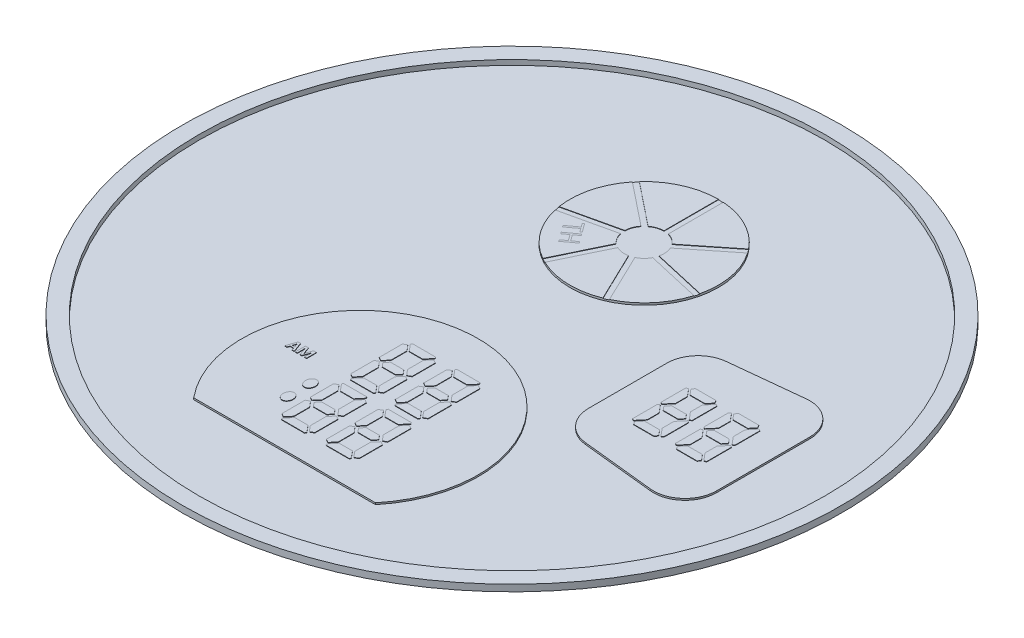
SolidWorks part; units mm, degrees
note: The reader was unsure of these and kept them because the rebuilt part matched: shared geometry of "Sketch2<5>".
ref_plane "Front Plane" through (0, 0, 0) normal (0, 0, 1) x (1, 0, 0)
ref_plane "Top Plane" through (0, 0, 0) normal (0, 1, 0) x (1, 0, 0)
ref_plane "Right Plane" through (0, 0, 0) normal (1, 0, 0) x (0, 0, -1)
sketch "Sketch1" plane through (0, 0, 0) normal (0, 1, 0) x (1, 0, 0)
  line L0 (13.2477, 3.3274) -> (8.8477, 2.8649) construction
  line L1 (13.8, -2.8301) -> (13.8, 2.8301) construction
  line L2 (8.8477, -2.8649) -> (13.2477, -3.3274) construction
  line L3 (8.4, 2.3677) -> (8.4, -2.3677) construction
  line L4 (13.2477, 3.3274) -> (8.8477, 2.8649)
  line L5 (13.8, -2.8301) -> (13.8, 2.8301)
  line L6 (8.8477, -2.8649) -> (13.2477, -3.3274)
  line L7 (8.4, 2.3677) -> (8.4, -2.3677)
  line L8 (-4.8, -12.3658) -> (4.8, -12.3658)
  circle A0 centre (0, 0) radius 19.95 construction
  circle A1 centre (0, 0) radius 19.95
  circle A2 centre (0, 8) radius 3.9422 construction
  circle A3 centre (0, 8) radius 3.9422
  arc A4 (4.8, -12.3658) -> (-4.8, -12.3658) centre (0, -9.2) ccw construction
  arc A5 (4.8, -12.3658) -> (-4.8, -12.3658) centre (0, -9.2) ccw
  arc A6 (13.8, 2.8301) -> (13.2477, 3.3274) centre (13.3, 2.8301) ccw construction
  arc A7 (8.8477, 2.8649) -> (8.4, 2.3677) centre (8.9, 2.3677) ccw construction
  arc A8 (13.2477, -3.3274) -> (13.8, -2.8301) centre (13.3, -2.8301) ccw construction
  arc A9 (8.4, -2.3677) -> (8.8477, -2.8649) centre (8.9, -2.3677) ccw construction
  arc A10 (13.8, 2.8301) -> (13.2477, 3.3274) centre (13.3, 2.8301) ccw
  arc A11 (8.8477, 2.8649) -> (8.4, 2.3677) centre (8.9, 2.3677) ccw
  arc A12 (13.2477, -3.3274) -> (13.8, -2.8301) centre (13.3, -2.8301) ccw
  arc A13 (8.4, -2.3677) -> (8.8477, -2.8649) centre (8.9, -2.3677) ccw
extrude "Boss-Extrude1" add sketch "Sketch1" along normal blind 0.1 contours A1 A13 L7 A11 L4 A10 L5 A12 L6 A5 L8 A3 | A3 | L8 A5 | L7 A13 L6 A12 L5 A10 L4 A11
sketch "Sketch2" plane through (0, 0.1, 0) normal (0, 1, 0) x (1, 0, 0)
  line L0 (-4.8, -12.3658) -> (4.8, -12.3658) construction
  line L1 (-4.8, -12.3658) -> (4.8, -12.3658) construction
  line L2 (13.2477, 3.3274) -> (8.8477, 2.8649) construction
  line L3 (13.8, -2.8301) -> (13.8, 2.8301) construction
  line L4 (8.8477, -2.8649) -> (13.2477, -3.3274) construction
  line L5 (8.4, 2.3677) -> (8.4, -2.3677) construction
  line L6 (13.2477, 3.3274) -> (8.8477, 2.8649) construction
  line L7 (13.8, -2.8301) -> (13.8, 2.8301) construction
  line L8 (8.8477, -2.8649) -> (13.2477, -3.3274) construction
  line L9 (8.4, 2.3677) -> (8.4, -2.3677) construction
  line L10 (0, 8) -> (0, 12.5) construction
  line L11 (0, 8) -> (-3.5182, 10.8057) construction
  line L12 (0, 8) -> (0, 12.5) construction
  line L13 (0, 8) -> (3.5182, 10.8057) construction
  line L14 (0, 8) -> (4.3872, 6.9987) construction
  line L15 (0, 8) -> (1.9525, 3.9456) construction
  line L16 (0, 8) -> (-1.9525, 3.9456) construction
  line L17 (0, 8) -> (-4.3872, 6.9987) construction
  line L18 (8, 2.3677) -> (8, -2.3677) construction
  line L19 (8.8059, -3.2627) -> (13.2059, -3.7252) construction
  line L20 (14.2, -2.8301) -> (14.2, 2.8301) construction
  line L21 (13.2059, 3.7252) -> (8.8059, 3.2627) construction
  line L22 (-5.0107, -12.7658) -> (5.0107, -12.7658) construction
  line L23 (-2.7, -4.1233) -> (-2.7, -12.3658) construction
  line L24 (-2.7, -8.3) -> (5.6791, -8.3) construction
  line L25 (-0.2, -6.2567) -> (-0.4893, -6.6014)
  line L26 (-0.4893, -6.6014) -> (-0.4893, -7.5553)
  line L27 (-0.4893, -7.5553) -> (-0.2, -7.9)
  line L28 (-0.2, -7.9) -> (0.0107, -7.7783)
  line L29 (0.0107, -7.7783) -> (0.0107, -6.3783)
  line L30 (0.0107, -6.3783) -> (-0.2, -6.2567)
  line L31 (-0.9329, -6.2167) -> (-0.442, -6.2167) construction
  line L32 (0.0107, -6.055) -> (-0.2, -6.1767)
  line L33 (-0.2, -6.1767) -> (-0.4893, -5.8319)
  line L34 (0.0107, -4.655) -> (0.0107, -6.055)
  line L35 (-0.2, -4.5333) -> (0.0107, -4.655)
  line L36 (-0.4893, -4.878) -> (-0.2, -4.5333)
  line L37 (-0.4893, -5.8319) -> (-0.4893, -4.878)
  line L38 (-0.5823, -7.6) -> (-0.2354, -8.0134)
  line L39 (-0.2354, -8.0134) -> (-0.2854, -8.1)
  line L40 (-0.2854, -8.1) -> (-1.6854, -8.1)
  line L41 (-1.6854, -8.1) -> (-1.7354, -8.0134)
  line L42 (-1.7354, -8.0134) -> (-1.3885, -7.6)
  line L43 (-1.3885, -7.6) -> (-0.5823, -7.6)
  line L44 (-0.3725, -6.2167) -> (-0.5823, -5.9667)
  line L45 (-0.5823, -5.9667) -> (-1.3885, -5.9667)
  line L46 (-1.3885, -5.9667) -> (-1.5983, -6.2167)
  line L47 (-1.5983, -6.2167) -> (-1.3885, -6.4667)
  line L48 (-1.3885, -6.4667) -> (-0.5823, -6.4667)
  line L49 (-0.5823, -6.4667) -> (-0.3725, -6.2167)
  line L50 (-1.3885, -5.9667) -> (-1.3885, -6.4667) construction
  line L51 (-0.9854, -7.6) -> (-0.9854, -7.1638) construction
  line L52 (-0.4893, -6.6014) -> (-0.4893, -7.5553)
  line L53 (-0.4893, -7.5553) -> (-0.2, -7.9)
  line L54 (-0.2, -7.9) -> (0.0107, -7.7783)
  line L55 (0.0107, -7.7783) -> (0.0107, -6.3783)
  line L56 (-0.2, -6.2567) -> (-0.4893, -6.6014)
  line L57 (0.0107, -6.3783) -> (-0.2, -6.2567)
  line L58 (0.0107, -6.055) -> (-0.2, -6.1767)
  line L59 (0.0107, -4.655) -> (0.0107, -6.055)
  line L60 (-0.2, -4.5333) -> (0.0107, -4.655)
  line L61 (-0.4893, -4.878) -> (-0.2, -4.5333)
  line L62 (-0.4893, -5.8319) -> (-0.4893, -4.878)
  line L63 (-0.2, -6.1767) -> (-0.4893, -5.8319)
  line L64 (-1.7708, -6.1767) -> (-1.4815, -5.8319)
  line L65 (-1.4815, -5.8319) -> (-1.4815, -4.878)
  line L66 (-1.4815, -4.878) -> (-1.7708, -4.5333)
  line L67 (-1.7708, -4.5333) -> (-1.9815, -4.655)
  line L68 (-1.9815, -4.655) -> (-1.9815, -6.055)
  line L69 (-1.9815, -6.055) -> (-1.7708, -6.1767)
  line L70 (-1.9815, -6.3783) -> (-1.7708, -6.2567)
  line L71 (-1.7708, -6.2567) -> (-1.4815, -6.6014)
  line L72 (-1.9815, -7.7783) -> (-1.9815, -6.3783)
  line L73 (-1.7708, -7.9) -> (-1.9815, -7.7783)
  line L74 (-1.4815, -7.5553) -> (-1.7708, -7.9)
  line L75 (-1.4815, -6.6014) -> (-1.4815, -7.5553)
  line L76 (-1.4815, -5.8319) -> (-1.4815, -4.878)
  line L77 (-1.4815, -4.878) -> (-1.7708, -4.5333)
  line L78 (-1.7708, -4.5333) -> (-1.9815, -4.655)
  line L79 (-1.9815, -4.655) -> (-1.9815, -6.055)
  line L80 (-1.7708, -6.1767) -> (-1.4815, -5.8319)
  line L81 (-1.9815, -6.055) -> (-1.7708, -6.1767)
  line L82 (-1.9815, -6.3783) -> (-1.7708, -6.2567)
  line L83 (-1.9815, -7.7783) -> (-1.9815, -6.3783)
  line L84 (-1.7708, -7.9) -> (-1.9815, -7.7783)
  line L85 (-1.4815, -7.5553) -> (-1.7708, -7.9)
  line L86 (-1.4815, -6.6014) -> (-1.4815, -7.5553)
  line L87 (-1.7708, -6.2567) -> (-1.4815, -6.6014)
  line L88 (-0.2354, -4.4199) -> (-0.2854, -4.3333)
  line L89 (-0.5823, -4.8333) -> (-0.2354, -4.4199)
  line L90 (-1.3885, -4.8333) -> (-0.5823, -4.8333)
  line L91 (-0.2854, -4.3333) -> (-1.6854, -4.3333)
  line L92 (-1.6854, -4.3333) -> (-1.7354, -4.4199)
  line L93 (-1.7354, -4.4199) -> (-1.3885, -4.8333)
  line L94 (0.3607, -9.2447) -> (0.3607, -7.3553) construction
  line L95 (1.7069, -7.6) -> (1.7069, -7.1638) construction
  line L96 (2.11, -5.9667) -> (2.11, -6.4667) construction
  line L97 (1.6544, -6.2167) -> (1.1635, -6.2167) construction
  line L98 (2.4569, -4.4199) -> (2.11, -4.8333)
  line L99 (2.4069, -4.3333) -> (2.4569, -4.4199)
  line L100 (1.0069, -4.3333) -> (2.4069, -4.3333)
  line L101 (2.11, -4.8333) -> (1.3038, -4.8333)
  line L102 (1.3038, -4.8333) -> (0.9569, -4.4199)
  line L103 (0.9569, -4.4199) -> (1.0069, -4.3333)
  line L104 (2.4923, -6.2567) -> (2.203, -6.6014)
  line L105 (2.203, -6.6014) -> (2.203, -7.5553)
  line L106 (2.203, -7.5553) -> (2.4923, -7.9)
  line L107 (2.4923, -7.9) -> (2.703, -7.7783)
  line L108 (2.703, -7.7783) -> (2.703, -6.3783)
  line L109 (2.703, -6.3783) -> (2.4923, -6.2567)
  line L110 (2.703, -6.055) -> (2.4923, -6.1767)
  line L111 (2.4923, -6.1767) -> (2.203, -5.8319)
  line L112 (2.703, -4.655) -> (2.703, -6.055)
  line L113 (2.4923, -4.5333) -> (2.703, -4.655)
  line L114 (2.203, -4.878) -> (2.4923, -4.5333)
  line L115 (2.203, -5.8319) -> (2.203, -4.878)
  line L116 (2.203, -6.6014) -> (2.203, -7.5553)
  line L117 (2.203, -7.5553) -> (2.4923, -7.9)
  line L118 (2.4923, -7.9) -> (2.703, -7.7783)
  line L119 (2.703, -7.7783) -> (2.703, -6.3783)
  line L120 (2.4923, -6.2567) -> (2.203, -6.6014)
  line L121 (2.703, -6.3783) -> (2.4923, -6.2567)
  line L122 (2.703, -6.055) -> (2.4923, -6.1767)
  line L123 (2.703, -4.655) -> (2.703, -6.055)
  line L124 (2.4923, -4.5333) -> (2.703, -4.655)
  line L125 (2.203, -4.878) -> (2.4923, -4.5333)
  line L126 (2.203, -5.8319) -> (2.203, -4.878)
  line L127 (2.4923, -6.1767) -> (2.203, -5.8319)
  line L128 (0.9215, -6.1767) -> (1.2107, -5.8319)
  line L129 (1.2107, -5.8319) -> (1.2107, -4.878)
  line L130 (1.2107, -4.878) -> (0.9215, -4.5333)
  line L131 (0.9215, -4.5333) -> (0.7107, -4.655)
  line L132 (0.7107, -4.655) -> (0.7107, -6.055)
  line L133 (0.7107, -6.055) -> (0.9215, -6.1767)
  line L134 (0.7107, -6.3783) -> (0.9215, -6.2567)
  line L135 (0.9215, -6.2567) -> (1.2107, -6.6014)
  line L136 (0.7107, -7.7783) -> (0.7107, -6.3783)
  line L137 (0.9215, -7.9) -> (0.7107, -7.7783)
  line L138 (1.2107, -7.5553) -> (0.9215, -7.9)
  line L139 (1.2107, -6.6014) -> (1.2107, -7.5553)
  line L140 (1.3038, -6.4667) -> (1.094, -6.2167)
  line L141 (2.11, -6.4667) -> (1.3038, -6.4667)
  line L142 (2.3198, -6.2167) -> (2.11, -6.4667)
  line L143 (2.11, -5.9667) -> (2.3198, -6.2167)
  line L144 (1.3038, -5.9667) -> (2.11, -5.9667)
  line L145 (1.094, -6.2167) -> (1.3038, -5.9667)
  line L146 (2.11, -7.6) -> (1.3038, -7.6)
  line L147 (2.4569, -8.0134) -> (2.11, -7.6)
  line L148 (2.4069, -8.1) -> (2.4569, -8.0134)
  line L149 (1.0069, -8.1) -> (2.4069, -8.1)
  line L150 (0.9569, -8.0134) -> (1.0069, -8.1)
  line L151 (1.3038, -7.6) -> (0.9569, -8.0134)
  line L152 (1.2107, -5.8319) -> (1.2107, -4.878)
  line L153 (1.2107, -4.878) -> (0.9215, -4.5333)
  line L154 (0.9215, -4.5333) -> (0.7107, -4.655)
  line L155 (0.7107, -4.655) -> (0.7107, -6.055)
  line L156 (0.9215, -6.1767) -> (1.2107, -5.8319)
  line L157 (0.7107, -6.055) -> (0.9215, -6.1767)
  line L158 (0.7107, -6.3783) -> (0.9215, -6.2567)
  line L159 (0.7107, -7.7783) -> (0.7107, -6.3783)
  line L160 (0.9215, -7.9) -> (0.7107, -7.7783)
  line L161 (1.2107, -7.5553) -> (0.9215, -7.9)
  line L162 (1.2107, -6.6014) -> (1.2107, -7.5553)
  line L163 (0.9215, -6.2567) -> (1.2107, -6.6014)
  line L164 (-0.4893, -7.0783) -> (0.0107, -7.0783) construction
  line L165 (-1.3885, -7.6) -> (-1.3885, -8.1) construction
  line L166 (-1.3885, -9) -> (-1.3885, -8.5) construction
  line L167 (-0.4893, -9.5217) -> (0.0107, -9.5217) construction
  line L168 (1.6544, -10.3833) -> (1.1635, -10.3833) construction
  line L169 (2.11, -10.6333) -> (2.11, -10.1333) construction
  line L170 (1.7069, -9) -> (1.7069, -9.4362) construction
  line L171 (-0.9854, -9) -> (-0.9854, -9.4362) construction
  line L172 (-1.3885, -10.6333) -> (-1.3885, -10.1333) construction
  line L173 (-0.9329, -10.3833) -> (-0.442, -10.3833) construction
  line L174 (0.9215, -10.3433) -> (1.2107, -9.9986)
  line L175 (1.2107, -9.9986) -> (1.2107, -9.0447)
  line L176 (1.2107, -9.0447) -> (0.9215, -8.7)
  line L177 (0.9215, -8.7) -> (0.7107, -8.8217)
  line L178 (0.7107, -8.8217) -> (0.7107, -10.2217)
  line L179 (0.7107, -10.2217) -> (0.9215, -10.3433)
  line L180 (0.7107, -10.545) -> (0.9215, -10.4233)
  line L181 (0.9215, -10.4233) -> (1.2107, -10.7681)
  line L182 (0.7107, -11.945) -> (0.7107, -10.545)
  line L183 (0.9215, -12.0667) -> (0.7107, -11.945)
  line L184 (1.2107, -11.722) -> (0.9215, -12.0667)
  line L185 (1.2107, -10.7681) -> (1.2107, -11.722)
  line L186 (1.3038, -9) -> (0.9569, -8.5866)
  line L187 (0.9569, -8.5866) -> (1.0069, -8.5)
  line L188 (1.0069, -8.5) -> (2.4069, -8.5)
  line L189 (2.4069, -8.5) -> (2.4569, -8.5866)
  line L190 (2.4569, -8.5866) -> (2.11, -9)
  line L191 (2.11, -9) -> (1.3038, -9)
  line L192 (1.094, -10.3833) -> (1.3038, -10.6333)
  line L193 (1.3038, -10.6333) -> (2.11, -10.6333)
  line L194 (2.11, -10.6333) -> (2.3198, -10.3833)
  line L195 (2.3198, -10.3833) -> (2.11, -10.1333)
  line L196 (2.11, -10.1333) -> (1.3038, -10.1333)
  line L197 (1.3038, -10.1333) -> (1.094, -10.3833)
  line L198 (1.2107, -9.9986) -> (1.2107, -9.0447)
  line L199 (1.2107, -9.0447) -> (0.9215, -8.7)
  line L200 (0.9215, -8.7) -> (0.7107, -8.8217)
  line L201 (0.7107, -8.8217) -> (0.7107, -10.2217)
  line L202 (0.9215, -10.3433) -> (1.2107, -9.9986)
  line L203 (0.7107, -10.2217) -> (0.9215, -10.3433)
  line L204 (0.7107, -10.545) -> (0.9215, -10.4233)
  line L205 (0.7107, -11.945) -> (0.7107, -10.545)
  line L206 (0.9215, -12.0667) -> (0.7107, -11.945)
  line L207 (1.2107, -11.722) -> (0.9215, -12.0667)
  line L208 (1.2107, -10.7681) -> (1.2107, -11.722)
  line L209 (0.9215, -10.4233) -> (1.2107, -10.7681)
  line L210 (2.4923, -10.4233) -> (2.203, -10.7681)
  line L211 (2.203, -10.7681) -> (2.203, -11.722)
  line L212 (2.203, -11.722) -> (2.4923, -12.0667)
  line L213 (2.4923, -12.0667) -> (2.703, -11.945)
  line L214 (2.703, -11.945) -> (2.703, -10.545)
  line L215 (2.703, -10.545) -> (2.4923, -10.4233)
  line L216 (2.703, -10.2217) -> (2.4923, -10.3433)
  line L217 (2.4923, -10.3433) -> (2.203, -9.9986)
  line L218 (2.703, -8.8217) -> (2.703, -10.2217)
  line L219 (2.4923, -8.7) -> (2.703, -8.8217)
  line L220 (2.203, -9.0447) -> (2.4923, -8.7)
  line L221 (2.203, -9.9986) -> (2.203, -9.0447)
  line L222 (2.203, -10.7681) -> (2.203, -11.722)
  line L223 (2.203, -11.722) -> (2.4923, -12.0667)
  line L224 (2.4923, -12.0667) -> (2.703, -11.945)
  line L225 (2.703, -11.945) -> (2.703, -10.545)
  line L226 (2.4923, -10.4233) -> (2.203, -10.7681)
  line L227 (2.703, -10.545) -> (2.4923, -10.4233)
  line L228 (2.703, -10.2217) -> (2.4923, -10.3433)
  line L229 (2.703, -8.8217) -> (2.703, -10.2217)
  line L230 (2.4923, -8.7) -> (2.703, -8.8217)
  line L231 (2.203, -9.0447) -> (2.4923, -8.7)
  line L232 (2.203, -9.9986) -> (2.203, -9.0447)
  line L233 (2.4923, -10.3433) -> (2.203, -9.9986)
  line L234 (0.9569, -12.1801) -> (1.0069, -12.2667)
  line L235 (1.3038, -11.7667) -> (0.9569, -12.1801)
  line L236 (2.11, -11.7667) -> (1.3038, -11.7667)
  line L237 (1.0069, -12.2667) -> (2.4069, -12.2667)
  line L238 (2.4069, -12.2667) -> (2.4569, -12.1801)
  line L239 (2.4569, -12.1801) -> (2.11, -11.7667)
  line L240 (-1.7354, -12.1801) -> (-1.3885, -11.7667)
  line L241 (-1.6854, -12.2667) -> (-1.7354, -12.1801)
  line L242 (-0.2854, -12.2667) -> (-1.6854, -12.2667)
  line L243 (-1.3885, -11.7667) -> (-0.5823, -11.7667)
  line L244 (-0.5823, -11.7667) -> (-0.2354, -12.1801)
  line L245 (-0.2354, -12.1801) -> (-0.2854, -12.2667)
  line L246 (-1.7708, -10.3433) -> (-1.4815, -9.9986)
  line L247 (-1.4815, -9.9986) -> (-1.4815, -9.0447)
  line L248 (-1.4815, -9.0447) -> (-1.7708, -8.7)
  line L249 (-1.7708, -8.7) -> (-1.9815, -8.8217)
  line L250 (-1.9815, -8.8217) -> (-1.9815, -10.2217)
  line L251 (-1.9815, -10.2217) -> (-1.7708, -10.3433)
  line L252 (-1.9815, -10.545) -> (-1.7708, -10.4233)
  line L253 (-1.7708, -10.4233) -> (-1.4815, -10.7681)
  line L254 (-1.9815, -11.945) -> (-1.9815, -10.545)
  line L255 (-1.7708, -12.0667) -> (-1.9815, -11.945)
  line L256 (-1.4815, -11.722) -> (-1.7708, -12.0667)
  line L257 (-1.4815, -10.7681) -> (-1.4815, -11.722)
  line L258 (-1.4815, -9.9986) -> (-1.4815, -9.0447)
  line L259 (-1.4815, -9.0447) -> (-1.7708, -8.7)
  line L260 (-1.7708, -8.7) -> (-1.9815, -8.8217)
  line L261 (-1.9815, -8.8217) -> (-1.9815, -10.2217)
  line L262 (-1.7708, -10.3433) -> (-1.4815, -9.9986)
  line L263 (-1.9815, -10.2217) -> (-1.7708, -10.3433)
  line L264 (-1.9815, -10.545) -> (-1.7708, -10.4233)
  line L265 (-1.9815, -11.945) -> (-1.9815, -10.545)
  line L266 (-1.7708, -12.0667) -> (-1.9815, -11.945)
  line L267 (-1.4815, -11.722) -> (-1.7708, -12.0667)
  line L268 (-1.4815, -10.7681) -> (-1.4815, -11.722)
  line L269 (-1.7708, -10.4233) -> (-1.4815, -10.7681)
  line L270 (-0.2, -10.4233) -> (-0.4893, -10.7681)
  line L271 (-0.4893, -10.7681) -> (-0.4893, -11.722)
  line L272 (-0.4893, -11.722) -> (-0.2, -12.0667)
  line L273 (-0.2, -12.0667) -> (0.0107, -11.945)
  line L274 (0.0107, -11.945) -> (0.0107, -10.545)
  line L275 (0.0107, -10.545) -> (-0.2, -10.4233)
  line L276 (0.0107, -10.2217) -> (-0.2, -10.3433)
  line L277 (-0.2, -10.3433) -> (-0.4893, -9.9986)
  line L278 (0.0107, -8.8217) -> (0.0107, -10.2217)
  line L279 (-0.2, -8.7) -> (0.0107, -8.8217)
  line L280 (-0.4893, -9.0447) -> (-0.2, -8.7)
  line L281 (-0.4893, -9.9986) -> (-0.4893, -9.0447)
  line L282 (-0.5823, -10.1333) -> (-0.3725, -10.3833)
  line L283 (-1.3885, -10.1333) -> (-0.5823, -10.1333)
  line L284 (-1.5983, -10.3833) -> (-1.3885, -10.1333)
  line L285 (-1.3885, -10.6333) -> (-1.5983, -10.3833)
  line L286 (-0.5823, -10.6333) -> (-1.3885, -10.6333)
  line L287 (-0.3725, -10.3833) -> (-0.5823, -10.6333)
  line L288 (-1.3885, -9) -> (-0.5823, -9)
  line L289 (-1.7354, -8.5866) -> (-1.3885, -9)
  line L290 (-1.6854, -8.5) -> (-1.7354, -8.5866)
  line L291 (-0.2854, -8.5) -> (-1.6854, -8.5)
  line L292 (-0.2354, -8.5866) -> (-0.2854, -8.5)
  line L293 (-0.5823, -9) -> (-0.2354, -8.5866)
  line L294 (-0.4893, -10.7681) -> (-0.4893, -11.722)
  line L295 (-0.4893, -11.722) -> (-0.2, -12.0667)
  line L296 (-0.2, -12.0667) -> (0.0107, -11.945)
  line L297 (0.0107, -11.945) -> (0.0107, -10.545)
  line L298 (-0.2, -10.4233) -> (-0.4893, -10.7681)
  line L299 (0.0107, -10.545) -> (-0.2, -10.4233)
  line L300 (0.0107, -10.2217) -> (-0.2, -10.3433)
  line L301 (0.0107, -8.8217) -> (0.0107, -10.2217)
  line L302 (-0.2, -8.7) -> (0.0107, -8.8217)
  line L303 (-0.4893, -9.0447) -> (-0.2, -8.7)
  line L304 (-0.4893, -9.9986) -> (-0.4893, -9.0447)
  line L305 (-0.2, -10.3433) -> (-0.4893, -9.9986)
  line L306 (-3.2476, -10.175) -> (-2.4, -10.175) construction
  line L307 (-5.4694, -8.3) -> (-3.8694, -8.3) construction
  line L308 (-4.8767, -8.3) -> (-5.0143, -8.3)
  line L309 (-5.0143, -8.3) -> (-5.0585, -8.161)
  line L310 (-5.0585, -8.161) -> (-5.2745, -8.161)
  line L311 (-5.2745, -8.161) -> (-5.318, -8.3)
  line L312 (-5.318, -8.3) -> (-5.4548, -8.3)
  line L313 (-5.4548, -8.3) -> (-5.2426, -7.7)
  line L314 (-5.2426, -7.7) -> (-5.0962, -7.7)
  line L315 (-5.0962, -7.7) -> (-4.8767, -8.3)
  line L316 (-5.0887, -8.0659) -> (-5.1602, -7.8554)
  line L317 (-5.1796, -7.8538) -> (-5.2467, -8.0659)
  line L318 (-5.2467, -8.0659) -> (-5.0887, -8.0659)
  line L319 (-4.2621, -8.3) -> (-4.2621, -7.9363)
  line L320 (-4.2517, -7.8098) -> (-4.2548, -7.8098)
  line L321 (-4.2735, -7.8867) -> (-4.4231, -8.3)
  line L322 (-4.4231, -8.3) -> (-4.5255, -8.3)
  line L323 (-4.5255, -8.3) -> (-4.6749, -7.8906)
  line L324 (-4.6938, -7.8098) -> (-4.6972, -7.8098)
  line L325 (-4.6938, -7.961) -> (-4.6938, -8.3)
  line L326 (-4.6938, -8.3) -> (-4.8109, -8.3)
  line L327 (-4.8109, -8.3) -> (-4.8109, -7.7)
  line L328 (-4.8109, -7.7) -> (-4.6206, -7.7)
  line L329 (-4.6206, -7.7) -> (-4.4925, -8.0627)
  line L330 (-4.4705, -8.1471) -> (-4.4679, -8.1471)
  line L331 (-4.4431, -8.0619) -> (-4.3133, -7.7)
  line L332 (-4.3133, -7.7) -> (-4.1377, -7.7)
  line L333 (-4.1377, -7.7) -> (-4.1377, -8.3)
  line L334 (-4.1377, -8.3) -> (-4.2621, -8.3)
  line L335 (10.6804, -0.0329) -> (10.2948, -0.4925)
  line L336 (10.2948, -0.4925) -> (10.2948, -1.2053)
  line L337 (10.2948, -1.2053) -> (10.6804, -1.6649)
  line L338 (10.6804, -1.6649) -> (10.7948, -1.5989)
  line L339 (10.7948, -1.5989) -> (10.7948, -0.0989)
  line L340 (10.7948, -0.0989) -> (10.6804, -0.0329)
  line L341 (10.4231, 0.0071) -> (10.9141, 0.0071) construction
  line L342 (10.7948, 0.1131) -> (10.6804, 0.0471)
  line L343 (10.6804, 0.0471) -> (10.2948, 0.5067)
  line L344 (10.7948, 1.6131) -> (10.7948, 0.1131)
  line L345 (10.6804, 1.6791) -> (10.7948, 1.6131)
  line L346 (10.2948, 1.2195) -> (10.6804, 1.6791)
  line L347 (10.2948, 0.5067) -> (10.2948, 1.2195)
  line L348 (10.2982, -1.3649) -> (10.5724, -1.6917)
  line L349 (10.5724, -1.6917) -> (10.4724, -1.8649)
  line L350 (10.4724, -1.8649) -> (9.2224, -1.8649)
  line L351 (9.2224, -1.8649) -> (9.1224, -1.6917)
  line L352 (9.1224, -1.6917) -> (9.3966, -1.3649)
  line L353 (9.3966, -1.3649) -> (10.2982, -1.3649)
  line L354 (10.5079, 0.0071) -> (10.2982, 0.2571)
  line L355 (10.2982, 0.2571) -> (9.3966, 0.2571)
  line L356 (9.3966, 0.2571) -> (9.1868, 0.0071)
  line L357 (9.1868, 0.0071) -> (9.3966, -0.2429)
  line L358 (9.3966, -0.2429) -> (10.2982, -0.2429)
  line L359 (10.2982, -0.2429) -> (10.5079, 0.0071)
  line L360 (9.3966, 0.2571) -> (9.3966, -0.2429) construction
  line L361 (9.8474, -1.3649) -> (9.8474, -1.1561) construction
  line L362 (10.2948, -0.4925) -> (10.2948, -1.2053)
  line L363 (10.2948, -1.2053) -> (10.6804, -1.6649)
  line L364 (10.6804, -1.6649) -> (10.7948, -1.5989)
  line L365 (10.7948, -1.5989) -> (10.7948, -0.0989)
  line L366 (10.6804, -0.0329) -> (10.2948, -0.4925)
  line L367 (10.7948, -0.0989) -> (10.6804, -0.0329)
  line L368 (10.7948, 0.1131) -> (10.6804, 0.0471)
  line L369 (10.7948, 1.6131) -> (10.7948, 0.1131)
  line L370 (10.6804, 1.6791) -> (10.7948, 1.6131)
  line L371 (10.2948, 1.2195) -> (10.6804, 1.6791)
  line L372 (10.2948, 0.5067) -> (10.2948, 1.2195)
  line L373 (10.6804, 0.0471) -> (10.2948, 0.5067)
  line L374 (9.0143, 0.0471) -> (9.4, 0.5067)
  line L375 (9.4, 0.5067) -> (9.4, 1.2195)
  line L376 (9.4, 1.2195) -> (9.0143, 1.6791)
  line L377 (9.0143, 1.6791) -> (8.9, 1.6131)
  line L378 (8.9, 1.6131) -> (8.9, 0.1131)
  line L379 (8.9, 0.1131) -> (9.0143, 0.0471)
  line L380 (8.9, -0.0989) -> (9.0143, -0.0329)
  line L381 (9.0143, -0.0329) -> (9.4, -0.4925)
  line L382 (8.9, -1.5989) -> (8.9, -0.0989)
  line L383 (9.0143, -1.6649) -> (8.9, -1.5989)
  line L384 (9.4, -1.2053) -> (9.0143, -1.6649)
  line L385 (9.4, -0.4925) -> (9.4, -1.2053)
  line L386 (9.4, 0.5067) -> (9.4, 1.2195)
  line L387 (9.4, 1.2195) -> (9.0143, 1.6791)
  line L388 (9.0143, 1.6791) -> (8.9, 1.6131)
  line L389 (8.9, 1.6131) -> (8.9, 0.1131)
  line L390 (9.0143, 0.0471) -> (9.4, 0.5067)
  line L391 (8.9, 0.1131) -> (9.0143, 0.0471)
  line L392 (8.9, -0.0989) -> (9.0143, -0.0329)
  line L393 (8.9, -1.5989) -> (8.9, -0.0989)
  line L394 (9.0143, -1.6649) -> (8.9, -1.5989)
  line L395 (9.4, -1.2053) -> (9.0143, -1.6649)
  line L396 (9.4, -0.4925) -> (9.4, -1.2053)
  line L397 (9.0143, -0.0329) -> (9.4, -0.4925)
  line L398 (10.5724, 1.7059) -> (10.4724, 1.8791)
  line L399 (10.2982, 1.3791) -> (10.5724, 1.7059)
  line L400 (9.3966, 1.3791) -> (10.2982, 1.3791)
  line L401 (10.4724, 1.8791) -> (9.2224, 1.8791)
  line L402 (9.2224, 1.8791) -> (9.1224, 1.7059)
  line L403 (9.1224, 1.7059) -> (9.3966, 1.3791)
  line L404 (11.1448, 0.7171) -> (11.1448, -2.2635) construction
  line L405 (12.8929, -1.3649) -> (12.8929, -1.8649) construction
  line L406 (11.9948, -0.8489) -> (11.4948, -0.8489) construction
  line L413 (12.4422, -1.3649) -> (12.4422, -1.1561) construction
  line L414 (12.8929, 0.2571) -> (12.8929, -0.2429) construction
  line L415 (11.8664, 0.0071) -> (11.3754, 0.0071) construction
  line L416 (13.1672, 1.7059) -> (12.8929, 1.3791)
  line L417 (13.0672, 1.8791) -> (13.1672, 1.7059)
  line L418 (11.8172, 1.8791) -> (13.0672, 1.8791)
  line L419 (12.8929, 1.3791) -> (11.9914, 1.3791)
  line L420 (11.9914, 1.3791) -> (11.7172, 1.7059)
  line L421 (11.7172, 1.7059) -> (11.8172, 1.8791)
  line L422 (13.2752, -0.0329) -> (12.8895, -0.4925)
  line L423 (12.8895, -0.4925) -> (12.8895, -1.2053)
  line L424 (12.8895, -1.2053) -> (13.2752, -1.6649)
  line L437 (13.2752, -1.6649) -> (13.3895, -1.5989)
  line L438 (13.3895, -1.5989) -> (13.3895, -0.0989)
  line L439 (13.3895, -0.0989) -> (13.2752, -0.0329)
  line L440 (13.3895, 0.1131) -> (13.2752, 0.0471)
  line L441 (13.2752, 0.0471) -> (12.8895, 0.5067)
  line L442 (13.3895, 1.6131) -> (13.3895, 0.1131)
  line L443 (13.2752, 1.6791) -> (13.3895, 1.6131)
  line L444 (12.8895, 1.2195) -> (13.2752, 1.6791)
  line L445 (12.8895, 0.5067) -> (12.8895, 1.2195)
  line L446 (12.8895, -0.4925) -> (12.8895, -1.2053)
  line L447 (12.8895, -1.2053) -> (13.2752, -1.6649)
  line L448 (13.2752, -1.6649) -> (13.3895, -1.5989)
  line L473 (10.2948, -0.8489) -> (10.7948, -0.8489) construction
  line L474 (9.3966, -1.3649) -> (9.3966, -1.8649) construction
  line L475 (13.3895, -1.5989) -> (13.3895, -0.0989)
  line L476 (13.2752, -0.0329) -> (12.8895, -0.4925)
  line L477 (13.3895, -0.0989) -> (13.2752, -0.0329)
  line L478 (13.3895, 0.1131) -> (13.2752, 0.0471)
  line L479 (13.3895, 1.6131) -> (13.3895, 0.1131)
  line L480 (13.2752, 1.6791) -> (13.3895, 1.6131)
  line L481 (12.8895, 1.2195) -> (13.2752, 1.6791)
  line L482 (12.8895, 0.5067) -> (12.8895, 1.2195)
  line L483 (13.2752, 0.0471) -> (12.8895, 0.5067)
  line L484 (11.6091, 0.0471) -> (11.9948, 0.5067)
  line L485 (11.9948, 0.5067) -> (11.9948, 1.2195)
  line L486 (11.9948, 1.2195) -> (11.6091, 1.6791)
  line L487 (11.6091, 1.6791) -> (11.4948, 1.6131)
  line L488 (11.4948, 1.6131) -> (11.4948, 0.1131)
  line L489 (11.4948, 0.1131) -> (11.6091, 0.0471)
  line L490 (11.4948, -0.0989) -> (11.6091, -0.0329)
  line L491 (11.6091, -0.0329) -> (11.9948, -0.4925)
  line L492 (11.4948, -1.5989) -> (11.4948, -0.0989)
  line L493 (11.6091, -1.6649) -> (11.4948, -1.5989)
  line L494 (11.9948, -1.2053) -> (11.6091, -1.6649)
  line L495 (11.9948, -0.4925) -> (11.9948, -1.2053)
  line L496 (11.9914, -0.2429) -> (11.7816, 0.0071)
  line L497 (12.8929, -0.2429) -> (11.9914, -0.2429)
  line L498 (13.1027, 0.0071) -> (12.8929, -0.2429)
  line L499 (12.8929, 0.2571) -> (13.1027, 0.0071)
  line L500 (11.9914, 0.2571) -> (12.8929, 0.2571)
  line L501 (11.7816, 0.0071) -> (11.9914, 0.2571)
  line L502 (12.8929, -1.3649) -> (11.9914, -1.3649)
  line L503 (13.1672, -1.6917) -> (12.8929, -1.3649)
  line L504 (13.0672, -1.8649) -> (13.1672, -1.6917)
  line L505 (11.8172, -1.8649) -> (13.0672, -1.8649)
  line L506 (11.7172, -1.6917) -> (11.8172, -1.8649)
  line L507 (11.9914, -1.3649) -> (11.7172, -1.6917)
  line L508 (11.9948, 0.5067) -> (11.9948, 1.2195)
  line L509 (11.9948, 1.2195) -> (11.6091, 1.6791)
  line L510 (11.6091, 1.6791) -> (11.4948, 1.6131)
  line L511 (11.4948, 1.6131) -> (11.4948, 0.1131)
  line L512 (11.6091, 0.0471) -> (11.9948, 0.5067)
  line L513 (11.4948, 0.1131) -> (11.6091, 0.0471)
  line L514 (11.4948, -0.0989) -> (11.6091, -0.0329)
  line L515 (11.4948, -1.5989) -> (11.4948, -0.0989)
  line L516 (11.6091, -1.6649) -> (11.4948, -1.5989)
  line L517 (11.9948, -1.2053) -> (11.6091, -1.6649)
  line L518 (11.9948, -0.4925) -> (11.9948, -1.2053)
  line L519 (11.6091, -0.0329) -> (11.9948, -0.4925)
  line L520 (0.3, 9.1619) -> (0.3, 12.49)
  line L521 (1.0955, 8.4899) -> (3.6975, 10.5649)
  line L522 (1.066, 7.449) -> (4.3107, 6.7084)
  line L523 (0.2338, 6.823) -> (1.6778, 3.8245)
  line L524 (-0.7744, 7.0833) -> (-2.2184, 4.0848)
  line L525 (-1.1995, 8.0339) -> (-4.4442, 7.2934)
  line L526 (-0.7214, 8.959) -> (-3.3234, 11.034)
  line L527 (0, 9.2) -> (0, 12.5)
  line L528 (0.9382, 8.7482) -> (3.5182, 10.8057)
  line L529 (1.1699, 7.733) -> (4.3872, 6.9987)
  line L530 (0.5207, 6.9188) -> (1.9525, 3.9456)
  line L531 (-0.5207, 6.9188) -> (-1.9525, 3.9456)
  line L532 (-1.1699, 7.733) -> (-4.3872, 6.9987)
  line L533 (-0.9382, 8.7482) -> (-3.5182, 10.8057)
  line L534 (8.7014, -4.2573) -> (13.1014, -4.7197)
  line L535 (15.2, -2.8301) -> (15.2, 2.8301)
  line L536 (13.1014, 4.7197) -> (8.7014, 4.2573)
  line L537 (7, 2.3677) -> (7, -2.3677)
  line L538 (-5.5023, -13.7658) -> (5.5023, -13.7658)
  circle A1 centre (0, 8) radius 4.5
  arc A2 (4.8, -12.3658) -> (-4.8, -12.3658) centre (0, -9.2) ccw construction
  arc A3 (4.8, -12.3658) -> (-4.8, -12.3658) centre (0, -9.2) ccw construction
  arc A4 (13.8, 2.8301) -> (13.2477, 3.3274) centre (13.3, 2.8301) ccw construction
  arc A5 (13.2477, -3.3274) -> (13.8, -2.8301) centre (13.3, -2.8301) ccw construction
  arc A6 (8.4, -2.3677) -> (8.8477, -2.8649) centre (8.9, -2.3677) ccw construction
  arc A7 (8.8477, 2.8649) -> (8.4, 2.3677) centre (8.9, 2.3677) ccw construction
  arc A8 (13.8, 2.8301) -> (13.2477, 3.3274) centre (13.3, 2.8301) ccw construction
  arc A9 (13.2477, -3.3274) -> (13.8, -2.8301) centre (13.3, -2.8301) ccw construction
  arc A10 (8.4, -2.3677) -> (8.8477, -2.8649) centre (8.9, -2.3677) ccw construction
  arc A11 (8.8477, 2.8649) -> (8.4, 2.3677) centre (8.9, 2.3677) ccw construction
  arc A12 (8, -2.3677) -> (8.8059, -3.2627) centre (8.9, -2.3677) ccw construction
  arc A13 (13.2059, -3.7252) -> (14.2, -2.8301) centre (13.3, -2.8301) ccw construction
  arc A14 (14.2, 2.8301) -> (13.2059, 3.7252) centre (13.3, 2.8301) ccw construction
  arc A15 (8.8059, 3.2627) -> (8, 2.3677) centre (8.9, 2.3677) ccw construction
  arc A16 (5.0107, -12.7658) -> (-5.0107, -12.7658) centre (0, -9.2) ccw construction
  circle A17 centre (0, 0) radius 19.95 construction
  circle A19 centre (0, 8) radius 1.2 construction
  arc A20 (-0.7214, 8.959) -> (0, 9.2) centre (0, 8) cw
  arc A21 (0.3, 9.1619) -> (0.9382, 8.7482) centre (0, 8) cw
  arc A22 (-1.1995, 8.0339) -> (-0.9367, 8.75) centre (0, 8) cw
  arc A23 (-0.7744, 7.0833) -> (-1.1699, 7.733) centre (0, 8) cw
  arc A24 (-0.5207, 6.9188) -> (0.4328, 6.8808) centre (0, 8) ccw
  arc A25 (0.5207, 6.9188) -> (1.066, 7.449) centre (0, 8) ccw
  arc A27 (1.1699, 7.733) -> (1.0955, 8.4899) centre (0, 8) ccw
  arc A28 (13.1014, -4.7197) -> (15.2, -2.8301) centre (13.3, -2.8301) ccw
  arc A29 (15.2, 2.8301) -> (13.1014, 4.7197) centre (13.3, 2.8301) ccw
  arc A30 (8.7014, 4.2573) -> (7, 2.3677) centre (8.9, 2.3677) ccw
  arc A31 (7, -2.3677) -> (8.7014, -4.2573) centre (8.9, -2.3677) ccw
  arc A32 (5.5023, -13.7658) -> (-5.5023, -13.7658) centre (0, -9.2) ccw
  ellipse E0 centre (-2.7, -9.5) end of major axis (-2.7, -9.875) minor radius 0.3
  ellipse E1 centre (-2.7, -10.85) end of major axis (-2.7, -10.475) minor radius 0.3
  spline S0 degree 3 poles (-5.1602, -7.8554) (-5.1625, -7.8478) (-5.1667, -7.8303) (-5.1685, -7.8124) (-5.1694, -7.8024) knots 0 0 0 0 0.443615 1 1 1 1
  spline S1 degree 2 poles (-5.1694, -7.8024) (-5.1716, -7.8287) (-5.1796, -7.8538) knots 0 0 0 1 1 1
  spline S2 degree 3 poles (-4.2621, -7.9363) (-4.2622, -7.9274) (-4.2616, -7.9136) (-4.2607, -7.8947) (-4.2595, -7.8792) (-4.258, -7.863) (-4.2557, -7.8397) (-4.2532, -7.8219) (-4.2517, -7.8098) knots 0 0 0 0 0.210621 0.325951 0.447739 0.576027 0.710756 1 1 1 1
  spline S3 degree 3 poles (-4.2548, -7.8098) (-4.2565, -7.8186) (-4.2593, -7.8312) (-4.2628, -7.8472) (-4.2652, -7.8574) (-4.2675, -7.8665) (-4.2701, -7.8761) (-4.2721, -7.8828) (-4.2735, -7.8867) knots 0 0 0 0 0.340692 0.488416 0.620345 0.737917 0.841171 1 1 1 1
  spline S4 degree 3 poles (-4.6749, -7.8906) (-4.6762, -7.8871) (-4.6779, -7.8811) (-4.6802, -7.8718) (-4.6825, -7.8626) (-4.6849, -7.8516) (-4.6888, -7.8339) (-4.6919, -7.8198) (-4.6938, -7.8098) knots 0 0 0 0 0.132433 0.227599 0.343804 0.477754 0.632761 1 1 1 1
  spline S5 degree 2 poles (-4.6972, -7.8098) (-4.6937, -7.8853) (-4.6938, -7.961) knots 0 0 0 1 1 1
  spline S6 degree 3 poles (-4.4925, -8.0627) (-4.4874, -8.077) (-4.4784, -8.1048) (-4.4726, -8.1334) (-4.4705, -8.1471) knots 0 0 0 0 0.522065 1 1 1 1
  spline S7 degree 3 poles (-4.4679, -8.1471) (-4.4642, -8.1317) (-4.4565, -8.1031) (-4.4478, -8.0748) (-4.4431, -8.0619) knots 0 0 0 0 0.535259 1 1 1 1
  point P29 (0, 8)
  point P72 (-1.3885, -6.2167)
  point P78 (-0.9854, -7.6)
  point P79 (-0.9854, -6.4667)
  point P150 (0.0107, -7.0783)
  point P162 (0.3607, -8.3)
  point P352 (9.3966, 0.0071)
  point P358 (9.8474, -1.3649)
  point P359 (9.8474, -0.2429)
  point P426 (10.7948, -0.8489)
  point P450 (0, 8)
  point P463 (0, 8)
  dimension "D4" = 9
  dimension "D21" = 0.75
  dimension "D48" = 2.4
  dimension "D1" = 51.429
  dimension "D3" = 8
  dimension "D7" = 140
  dimension "D8" = 140
  dimension "D9" = 0.5
  dimension "D10" = 120
  dimension "D11" = 0.4
  dimension "D12" = 1.4
  dimension "D13" = 2.5
  dimension "D14" = 2.7
  dimension "D15" = 0.9
  dimension "D16" = 0.45
  dimension "D17" = 0.04
  dimension "D18" = 1.4
  dimension "D19" = 0.7
  dimension "D20" = 130
  dimension "D22" = 0.1
  dimension "D23" = 0.6
  dimension "D24" = 120
  dimension "D25" = 120
  dimension "D26" = 0.1
  dimension "D27" = 0.35
  dimension "D28" = 1.2
  dimension "D29" = 0.3
  dimension "D30" = 1.6
  dimension "D31" = 140
  dimension "D32" = 140
  dimension "D33" = 120
  dimension "D34" = 0.04
  dimension "D35" = 130
  dimension "D36" = 0.1
  dimension "D37" = 120
  dimension "D38" = 0.5
  dimension "D39" = 0.5
  dimension "D40" = 1
  dimension "D41" = 1.5
  dimension "D42" = 0.6
  dimension "D43" = 120
  dimension "D44" = 1.25
  dimension "D45" = 0.2
  dimension "D46" = 1.2
  dimension "D47" = 0.35
  dimension "D49" = 0.3
  dimension "D5" = 0.4
  dimension "D6" = 0.4
  dimension "D52" = 1
  dimension "D53" = 1
  dimension "D2" = 7
  dimension "D50" = 7
  dimension "D51" = 7
extrude "Boss-Extrude2" add sketch "Sketch2" along normal blind 0.1 contours A32 L538 | A28 L535 A29 L536 A30 L537 A31 L534 | A1
extrude "Boss-Extrude3" add sketch "Sketch2<5>" along normal blind 0.125 contours L385 L381 L380 L382 L383 L384 | L378 L379 L374 L375 L376 L377 | L402 L403 L400 L399 L398 L401 | L358 L359 L354 L355 L356 L357 | L347 L343 L342 L344 L345 L346 | L339 L340 L335 L336 L337 L338 | L353 L352 L351 L350 L349 L348 | L502 L507 L506 L505 L504 L503 | L495 L491 L490 L492 L493 L494 | L438 L439 L422 L423 L424 L437 | L501 L496 L497 L498 L499 L500 | L488 L489 L484 L485 L486 L487 | L421 L420 L419 L416 L417 L418 | L445 L441 L440 L442 L443 L444 | L75 L71 L70 L72 L73 L74 | L48 L49 L44 L45 L46 L47 | L68 L69 L64 L65 L66 L67 | L37 L33 L32 L34 L35 L36 | L29 L30 L25 L26 L27 L28 | L43 L42 L41 L40 L39 L38 | L288 L293 L292 L291 L290 L289 | L250 L251 L246 L247 L248 L249 | L257 L253 L252 L254 L255 L256 | L287 L282 L283 L284 L285 L286 | L281 L277 L276 L278 L279 L280 | L274 L275 L270 L271 L272 L273 | L245 L244 L243 L240 L241 L242 | L238 L239 L236 L235 L234 L237 | L185 L181 L180 L182 L183 L184 | L196 L197 L192 L193 L194 L195 | L214 L215 L210 L211 L212 L213 | L221 L217 L216 L218 L219 L220 | L178 L179 L174 L175 L176 L177 | L191 L190 L189 L188 L187 L186 | L146 L151 L150 L149 L148 L147 | L108 L109 L104 L105 L106 L107 | L139 L135 L134 L136 L137 L138 | L145 L140 L141 L142 L143 L144 | L115 L111 L110 L112 L113 L114 | L132 L133 L128 L129 L130 L131 | L103 L102 L101 L98 L99 L100 | E0 | E1 | L315 L314 L313 L312 L311 L310 L309 L308 S1 S0 L316 L318 L317 | S7 L330 S6 L329 L328 L327 L326 L325 S5 L324 S4 L323 L322 L321 S3 L320 S2 L319 L334 L333 L332 L331 | L525 A22 L533 A1 | L524 A23 L532 A1 | A24 L531 A1 L523 | A25 L530 A1 L522 | A27 L529 A1 L521 | L520 A21 L528 A1 | L526 A20 L527 A1 | L92 L93 L90 L89 L88 L91
sketch "Sketch2<5>" plane through (0, 0.1, 0) normal (0, 1, 0) x (1, 0, 0) same geometry as "Sketch2"
sketch "Sketch3" plane through (0, 0.225, 0) normal (0, 1, 0) x (1, 0, 0)
  line L0 (-3.5086, 6.6561) -> (-2.4835, 5.2491) construction
  text T0 "TH" font "Microsoft YaHei" height 0.9
split line "Split Line2"
sketch "Sketch4" plane through (0, 0.1, 0) normal (0, 1, 0) x (1, 0, 0)
  circle A0 centre (0, 0) radius 18.95
  circle A1 centre (0, 0) radius 19.95
  circle A2 centre (0, 0) radius 19.95
  dimension "D1" = 0
  dimension "D2" = 1
extrude "Boss-Extrude4" add sketch "Sketch4" along normal blind 0.3
